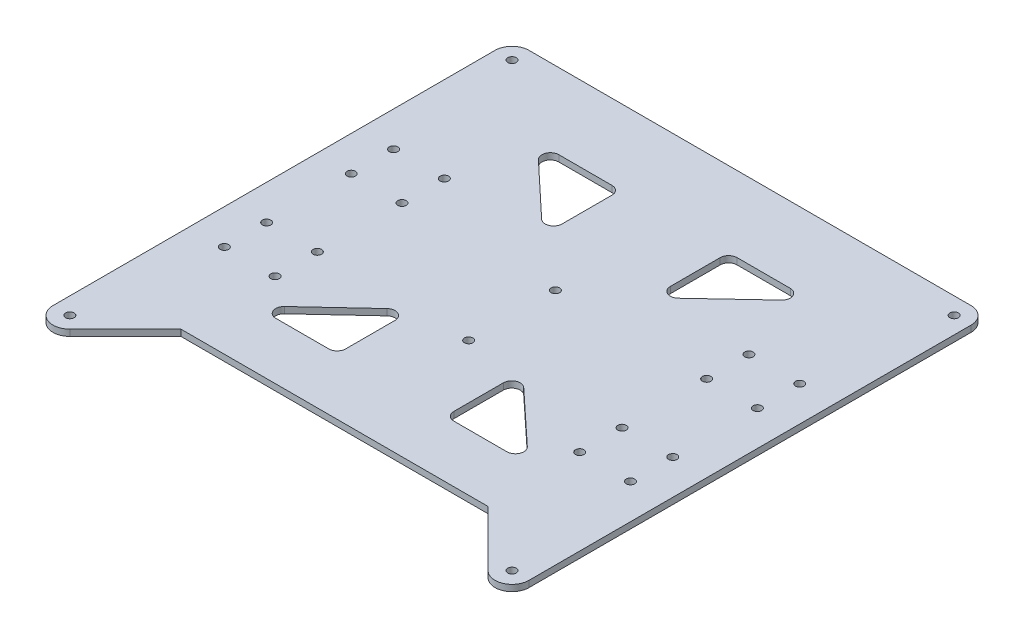
SolidWorks part; units mm, degrees
ref_plane "Front Plane" through (0, 0, 0) normal (0, 0, 1) x (1, 0, 0)
ref_plane "Top Plane" through (0, 0, 0) normal (0, 1, 0) x (1, 0, 0)
ref_plane "Right Plane" through (0, 0, 0) normal (1, 0, 0) x (0, 0, -1)
sketch "Sketch1" plane through (0, 0, 0) normal (0, 1, 0) x (1, 0, 0)
  line L0 (25.5785, 40) -> (25.5785, 76.8339)
  line L1 (25.5785, 76.8339) -> (64.8089, 76.8339)
  line L2 (-1061.5, 0) -> (48938.5, 0) construction
  line L3 (0, 112.5) -> (0, 22.5)
  line L4 (64.8089, 76.8339) -> (25.5785, 40)
  line L5 (25.5785, -20.5001) -> (25.5785, -57.0616)
  line L6 (112.5, 104.5) -> (112.5, 0)
  line L7 (25.5785, -57.0616) -> (64.8089, -57.0616)
  line L8 (64.8089, -57.0616) -> (25.5785, -20.5001)
  line L9 (0, 18.5) -> (0, -18.5001)
  line L10 (0, -22.5001) -> (0, -83.9069)
  line L13 (0, -83.9069) -> (72.5931, -83.9069)
  line L15 (112.5, 0) -> (112.5, -104.5)
  line L30 (98.8431, -110.1569) -> (72.5931, -83.9069)
  line L44 (104.5, 112.5) -> (0, 112.5)
  arc A1 (0, 18.5) -> (0, 22.5) centre (0, 20.5) ccw
  arc A3 (0, -18.5001) -> (0, -22.5001) centre (0, -20.5001) cw
  circle A5 centre (104.5, 104.5) radius 2
  circle A6 centre (104.5, -104.5) radius 2
  arc A7 (112.5, -104.5) -> (98.8431, -110.1569) centre (104.5, -104.5) cw
  arc A8 (112.5, 104.5) -> (104.5, 112.5) centre (104.5, 104.5) ccw
  circle A18 centre (96, 40) radius 2
  circle A19 centre (72, 40) radius 2
  circle A20 centre (72, 20) radius 2
  circle A21 centre (96, 20) radius 2
  circle A22 centre (96, -40) radius 2
  circle A23 centre (72, -40) radius 2
  circle A24 centre (72, -20) radius 2
  circle A25 centre (96, -20) radius 2
  point P21 (0, -61.4069)
  point P23 (0, 0)
  point P26 (0, -35)
  point P31 (25.5785, 0)
  point P42 (0, -83.9069)
  point P63 (0, 61.4068)
  point P68 (0, 83.9068)
  point P71 (0, 35)
  point P72 (61.5, 0)
extrude "Boss-Extrude2" add sketch "Sketch1" along normal blind 3
fillet "Fillet1" radius 4 6 edges at (64.8089, 1.5, 57.0616) (25.5785, 1.5, 57.0616) (25.5785, 1.5, 20.5001) (25.5785, 1.5, -40) (25.5785, 1.5, -76.8339) (64.8089, 1.5, -76.8339)
mirror "Mirror1" about plane through (0, 3, -112.5) normal (1, 0, 0) of "Fillet1", "Boss-Extrude2"
